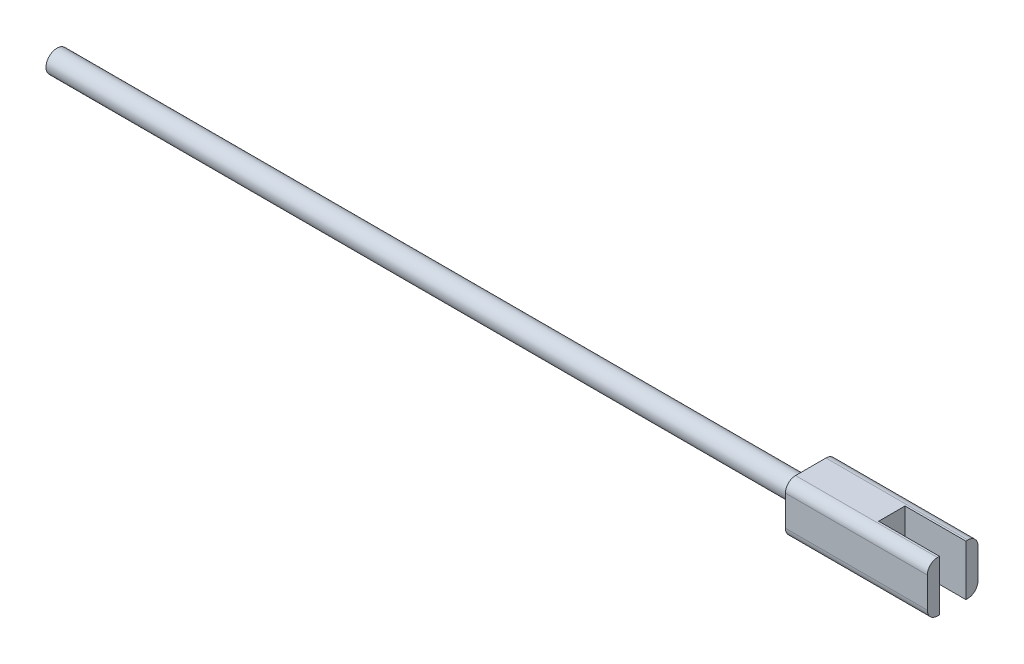
SolidWorks part; units mm, degrees
ref_plane "Front Plane" through (0, 0, 0) normal (0, 0, 1) x (1, 0, 0)
ref_plane "Top Plane" through (0, 0, 0) normal (0, 1, 0) x (1, 0, 0)
ref_plane "Right Plane" through (0, 0, 0) normal (1, 0, 0) x (0, 0, -1)
sketch "Sketch1" plane through (0, 0, 0) normal (1, 0, 0) x (0, 0, -1)
  circle A0 centre (0, 0) radius 1.09
extrude "Boss-Extrude1" add sketch "Sketch1" along normal blind 76.354
ref_plane "Plane1" through (74.354, 0, 0) normal (1, 0, 0) x (0, 0, -1)
sketch "Sketch2" plane through (74.354, 0, 0) normal (1, 0, 0) x (0, 0, -1)
  line L0 (-1.5, -2.5) -> (1.5, -2.5)
  line L1 (2.5, -1.5) -> (2.5, 1.5)
  line L2 (1.5, 2.5) -> (-1.5, 2.5)
  line L3 (-2.5, 1.5) -> (-2.5, -1.5)
  arc A0 (1.5, -2.5) -> (2.5, -1.5) centre (1.5, -1.5) ccw
  arc A1 (2.5, 1.5) -> (1.5, 2.5) centre (1.5, 1.5) ccw
  arc A2 (-1.5, 2.5) -> (-2.5, 1.5) centre (-1.5, 1.5) ccw
  arc A3 (-2.5, -1.5) -> (-1.5, -2.5) centre (-1.5, -1.5) ccw
extrude "Boss-Extrude2" add sketch "Sketch2" along normal blind 14
sketch "Sketch3" plane through (0, 0, 0) normal (0, 1, 0) x (1, 0, 0)
  line L0 (82.354, 1.3) -> (89.354, 1.3)
  line L1 (89.354, 1.3) -> (89.354, -1.3)
  line L2 (89.354, -1.3) -> (82.354, -1.3)
  line L3 (82.354, -1.3) -> (82.354, 1.3)
extrude "Cut-Extrude1" cut sketch "Sketch3" against normal through all and the other way through all
